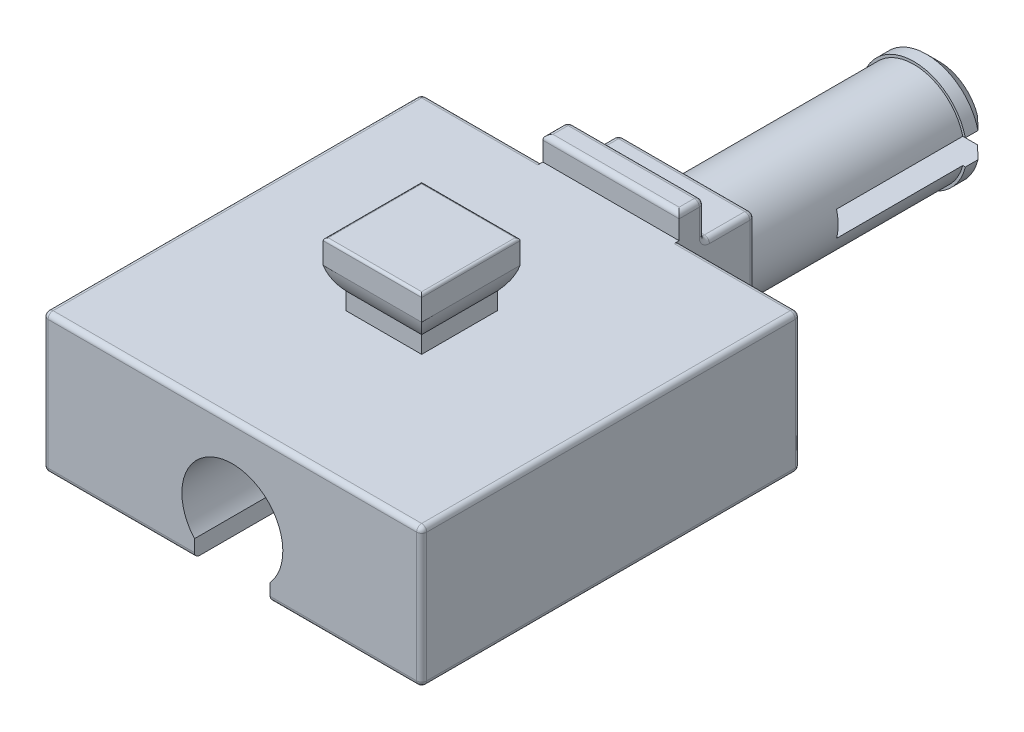
SolidWorks part; units mm, degrees
ref_plane "前视基准面" through (0, 0, 0) normal (0, 0, 1) x (1, 0, 0)
ref_plane "上视基准面" through (0, 0, 0) normal (0, 1, 0) x (1, 0, 0)
ref_plane "右视基准面" through (0, 0, 0) normal (1, 0, 0) x (0, 0, -1)
sketch "草图1" plane through (0, 0, 0) normal (0, 1, 0) x (1, 0, 0)
  line L0 (7.5, 7.5) -> (7.5, -7.5)
  line L1 (7.5, 7.5) -> (-7.5, 7.5)
  line L2 (7.5, -7.5) -> (-7.5, -7.5)
  line L3 (-7.5, 7.5) -> (-7.5, -7.5)
  line L4 (7.5, 7.5) -> (-7.5, -7.5) construction
  line L5 (7.5, -7.5) -> (-7.5, 7.5) construction
  point P1 (0, 0)
  dimension "D1" = 15
  dimension "D2" = 15
extrude "凸台-拉伸1" add sketch "草图1" along normal blind 5.5
sketch "草图2" plane through (0, 0, 7.5) normal (0, 0, 1) x (1, 0, 0)
  line L0 (0, 0) -> (0, 2) construction
  line L1 (1.5, 0) -> (-1.5, 0)
  line L2 (-7.5, 0) -> (7.5, 0) construction
  line L3 (-1.5, 0) -> (-1.5, 0.6771)
  line L4 (1.5, 0) -> (1.5, 0.6771)
  arc A0 (1.5, 0.6771) -> (-1.5, 0.6771) centre (0, 2) ccw
  dimension "D1" = 2
  dimension "D2" = 1.5
extrude "切除-拉伸1" cut sketch "草图2" against normal blind 11
sketch "草图3" plane through (0, 0, 0) normal (0, 0, 1) x (1, 0, 0)
  line L0 (0, 5.5) -> (0, 7.5) construction
  line L1 (-7.5, 5.5) -> (7.5, 5.5) construction
  line L2 (0, 7.5) -> (0, 8) construction
  line L3 (1.5, 5.5) -> (-1.5, 5.5)
  line L4 (-1.5, 5.5) -> (-1.5, 6.1771)
  line L5 (1.95, 8) -> (-1.95, 8)
  line L6 (-1.95, 8) -> (-1.95, 7.0556)
  line L7 (1.5, 5.5) -> (1.5, 6.1771)
  line L8 (1.95, 8) -> (1.95, 7.0556)
  arc A0 (-1.95, 7.0556) -> (-1.5, 6.1771) centre (0, 7.5) ccw
  arc A1 (1.95, 7.0556) -> (1.5, 6.1771) centre (0, 7.5) cw
  dimension "D5" = 2
  dimension "D1" = 2
  dimension "D2" = 0.5
  dimension "D3" = 1.5
  dimension "D4" = 1.95
extrude "凸台-拉伸2" add sketch "草图3" along normal blind 2 and the other way blind 2
sketch "草图4" plane through (0, 0, 0) normal (1, 0, 0) x (0, 0, -1)
  line L0 (0, 5.5) -> (0, 7.5) construction
  line L1 (2, 5.5) -> (-2, 5.5) construction
  line L2 (0, 7.5) -> (0, 8) construction
  line L3 (2, 8) -> (-2, 8) construction
  line L5 (0, 5.5) -> (-1.5, 5.5) construction
  line L6 (-7.5, 5.5) -> (7.5, 5.5) construction
  line L7 (-1.5, 5.5) -> (-1.5, 6.1771)
  line L8 (0, 8) -> (-1.95, 8) construction
  line L9 (-1.95, 8) -> (-1.95, 7.0556)
  line L10 (-1.95, 8) -> (-2, 8)
  line L11 (-2, 8) -> (-2, 5.5)
  line L12 (-2, 5.5) -> (-1.5, 5.5)
  line L13 (2, 5.5) -> (1.5, 5.5)
  line L14 (1.5, 5.5) -> (1.5, 6.1771)
  line L15 (1.95, 8) -> (1.95, 7.0556)
  line L16 (2, 8) -> (2, 5.5)
  line L17 (1.95, 8) -> (2, 8)
  arc A0 (-1.95, 7.0556) -> (-1.5, 6.1771) centre (0, 7.5) ccw
  arc A1 (1.95, 7.0556) -> (1.5, 6.1771) centre (0, 7.5) cw
  dimension "D4" = 2
  dimension "D1" = 2
  dimension "D2" = 1.95
  dimension "D3" = 1.5
extrude "切除-拉伸2" cut sketch "草图4" against normal blind 2 and the other way blind 2
sketch "草图5" plane through (0, 0, -7.5) normal (0, 0, -1) x (-1, 0, 0)
  line L0 (0, 0) -> (0, 2.75) construction
  line L1 (2.7, 6.45) -> (-2.7, 6.45)
  line L2 (2.7, 6.45) -> (2.7, -0.95)
  line L3 (-2.7, 6.45) -> (-2.7, -0.95)
  line L4 (2.7, -0.95) -> (-2.7, -0.95)
  line L5 (2.7, 6.45) -> (-2.7, -0.95) construction
  line L6 (-2.7, 6.45) -> (2.7, -0.95) construction
  dimension "D1" = 2.75
  dimension "D2" = 5.4
  dimension "D3" = 7.4
extrude "凸台-拉伸3" add sketch "草图5" along normal blind 1
sketch "草图6" plane through (0, 0, -8.5) normal (0, 0, -1) x (-1, 0, 0)
  line L0 (2.7, -0.95) -> (2.7, 6.45) construction
  line L1 (-2.7, 0) -> (2.7, 0)
  line L2 (-2.7, 0) -> (-2.7, 5)
  line L3 (-2.7, 5) -> (2.7, 5)
  line L4 (2.7, 0) -> (2.7, 5)
  dimension "D1" = 5
extrude "凸台-拉伸4" add sketch "草图6" along normal blind 2
sketch "草图7" plane through (0, 0, -10.5) normal (0, 0, -1) x (-1, 0, 0)
  line L0 (0, 0) -> (0, 2.2) construction
  circle A0 centre (0, 2.2) radius 2
  dimension "D2" = 4
  dimension "D1" = 2.2
extrude "凸台-拉伸5" add sketch "草图7" along normal blind 10
sketch "草图8" plane through (0, 0, -20.5) normal (0, 0, -1) x (-1, 0, 0)
  circle A0 centre (0, 2.2) radius 2.1
  dimension "D1" = 4.2
extrude "凸台-拉伸6" add sketch "草图8" against normal blind 1
chamfer "倒角1" distance 0.5 angle 45 1 edges at (-2.1, 2.2, -20.5)
sketch "草图9" plane through (0, 0, -20.5) normal (0, 0, -1) x (-1, 0, 0)
  line L0 (2.5, 2.7) -> (2.5, 1.7)
  line L1 (2.5, 2.7) -> (-2.5, 2.7)
  line L2 (2.5, 1.7) -> (-2.5, 1.7)
  line L3 (-2.5, 2.7) -> (-2.5, 1.7)
  line L4 (2.5, 2.7) -> (-2.5, 1.7) construction
  line L5 (2.5, 1.7) -> (-2.5, 2.7) construction
  point P1 (0, 2.2)
  dimension "D1" = 1
  dimension "D2" = 5
extrude "切除-拉伸3" cut sketch "草图9" against normal blind 6
fillet "圆角1" radius 0.1 4 edges at (0, 8, -1.95) (1.95, 8, 0) (0, 8, 1.95) (-1.95, 8, 0)
fillet "圆角2" radius 0.2 37 edges at (0, 5, -10.5) (0, 0, -10.5) (2.7, -0.95, -8) (0, -0.95, -8.5) (-2.7, -0.95, -8) (0, -0.95, -7.5) (-2.7, 6.45, -8) (0, 6.45, -8.5) (2.7, 6.45, -8) (0, 6.45, -7.5) (-7.5, 2.75, -7.5) (-7.5, 5.5, 0) (-7.5, 2.75, 7.5) (-7.5, 0, 0) (7.5, 2.75, 7.5) (7.5, 5.5, 0) (7.5, 2.75, -7.5) (7.5, 0, 0) (-2.7, 2.5, -10.5) (2.7, 2.5, -10.5) (-5.1, 0, -7.5) (5.1, 0, -7.5) (5.1, 5.5, -7.5) (-5.1, 5.5, -7.5) (4.5, 0, 7.5) (-4.5, 0, 7.5) (0, 5.5, 7.5)
